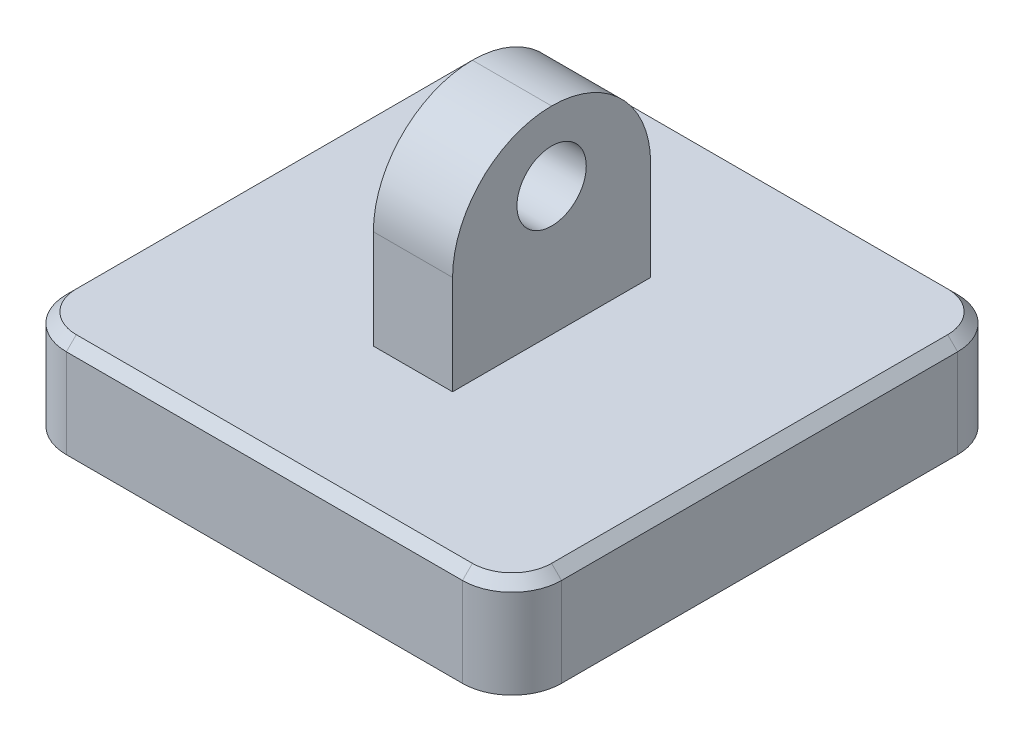
SolidWorks part; units mm, degrees
material "ABS"
ref_plane "Alzado" through (0, 0, 0) normal (0, 0, 1) x (1, 0, 0)
ref_plane "Planta" through (0, 0, 0) normal (0, 1, 0) x (1, 0, 0)
ref_plane "Vista lateral" through (0, 0, 0) normal (1, 0, 0) x (0, 0, -1)
sketch "Croquis1" plane through (0, 0, 0) normal (0, 1, 0) x (1, 0, 0)
  line L1 (-25, -25) -> (25, -25)
  line L2 (-25, -25) -> (-25, 25)
  line L3 (-25, 25) -> (25, 25)
  line L4 (25, -25) -> (25, 25)
  line L5 (-25, -25) -> (25, 25) construction
  line L6 (-25, 25) -> (25, -25) construction
  point P0 (0, 0)
  dimension "D1" = 50
  dimension "D2" = 50
extrude "Saliente-Extruir1" add sketch "Croquis1" along normal blind 10
sketch "Croquis2" plane through (0, 10, 0) normal (0, 1, 0) x (1, 0, 0)
  line L1 (4, 10) -> (-4, 10)
  line L2 (4, 10) -> (4, -10)
  line L3 (4, -10) -> (-4, -10)
  line L4 (-4, 10) -> (-4, -10)
  line L5 (4, 10) -> (-4, -10) construction
  line L6 (4, -10) -> (-4, 10) construction
  point P0 (0, 0)
  dimension "D1" = 8
  dimension "D2" = 20
extrude "Saliente-Extruir2" add sketch "Croquis2" along normal blind 20
sketch "Croquis3" plane through (4, 0, 0) normal (1, 0, 0) x (0, 0, -1)
  line L0 (0, 30) -> (0, 10) construction
  line L1 (-10, 30) -> (10, 30) construction
  line L2 (-10, 10) -> (10, 10) construction
  circle A0 centre (0, 23) radius 3.5
  dimension "D1" = 7
  dimension "D2" = 7
extrude "Cortar-Extruir1" cut sketch "Croquis3" against normal through all
fillet "Redondeo1" radius 10 2 edges at (0, 30, -10) (0, 30, 10)
fillet "Redondeo2" radius 5 4 edges at (-25, 5, -25) (25, 5, -25) (25, 5, 25) (-25, 5, 25)
chamfer "Chaflán1" distance 1 angle 45 8 edges at (-23.5355, 10, 23.5355) (-25, 10, 0) (-23.5355, 10, -23.5355) (0, 10, -25) (23.5355, 10, -23.5355) (25, 10, 0) (23.5355, 10, 23.5355) (0, 10, 25)
